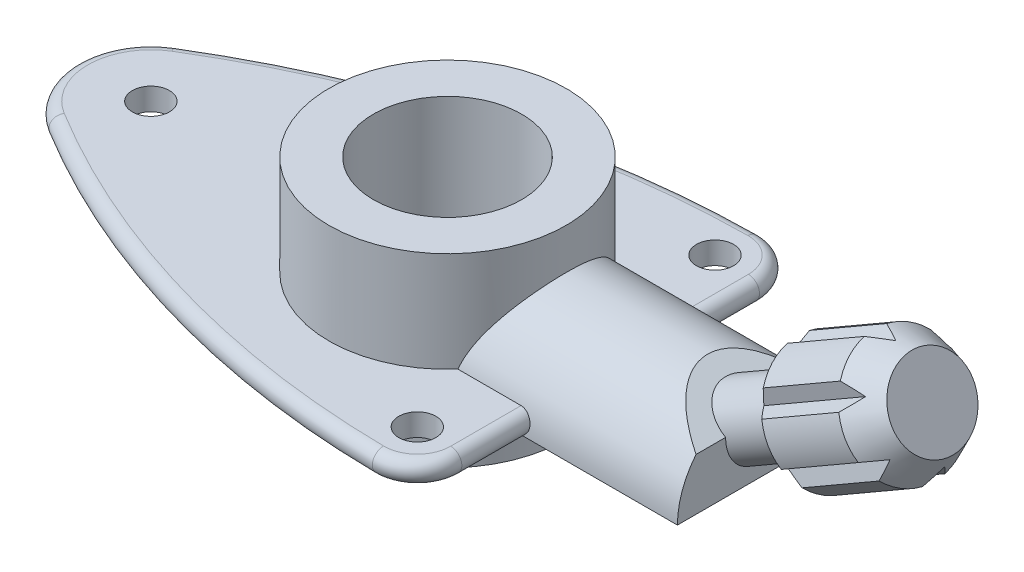
SolidWorks part; units mm, degrees
ref_plane "前视基准面" through (0, 0, 0) normal (0, 0, 1) x (1, 0, 0)
ref_plane "上视基准面" through (0, 0, 0) normal (0, 1, 0) x (1, 0, 0)
ref_plane "右视基准面" through (0, 0, 0) normal (1, 0, 0) x (0, 0, -1)
other "Configuration Table"
sketch "草图5" plane through (0, 0, 0) normal (0, 1, 0) x (1, 0, 0)
  line L0 (22, 20.0702) -> (22, -12.9012)
  line L1 (-61.685, 0) -> (42.0695, 0) construction
  line L3 (22, -20.0702) -> (22, 12.9012)
  line L4 (15.9338, 26.0698) -> (-45.2053, 8.5384) construction
  line L5 (15.9338, -26.0698) -> (-45.2053, -8.5384) construction
  circle A0 centre (0, 0) radius 10
  circle A1 centre (0, 0) radius 16
  arc A2 (22, 20.0702) -> (15.9338, 26.0698) centre (16, 20.0702) ccw
  arc A3 (15.9338, 26.0698) -> (-45.2053, 8.5384) centre (17.2581, -93.9229) ccw
  arc A4 (22, -20.0702) -> (15.9338, -26.0698) centre (16, -20.0702) cw
  arc A5 (15.9338, -26.0698) -> (-45.2053, -8.5384) centre (17.2581, 93.9229) cw
  arc A6 (-45.2053, 8.5384) -> (-45.2053, -8.5384) centre (-40, 0) ccw
  circle A7 centre (16, 20.0702) radius 2.5
  circle A8 centre (16, -20.0702) radius 2.5
  circle A9 centre (-40, 0) radius 2.5
  point P12 (-50, 0)
  dimension "D2" = 6
  dimension "D3" = 120
  dimension "D6" = 32
  dimension "D7" = 20
  dimension "D8" = 10
  dimension "D9" = 5
  dimension "D1" = 22
  dimension "D4" = 16
  dimension "D5" = 72
extrude "凸台-拉伸4" add sketch "草图5" along normal mid plane 3 contours A3 A6 A5 A4 L3 L0 A2 A1 region at (21.111, 0, -16.4857)
extrude "凸台-拉伸5" add sketch "草图5<5>" against normal blind 10 and the other way blind 15 contours A1 A0 region at (-15.5475, 0, 0)
sketch "草图5<5>" plane through (0, 0, 0) normal (0, 1, 0) x (1, 0, 0) same geometry as "草图5"
sketch "草图7" plane through (0, 0, 0) normal (1, 0, 0) x (0, 0, -1)
  line L0 (0, 27.4984) -> (0, -26.9284) construction
  line L1 (-11, -1.5) -> (11, -1.5)
  line L2 (-20.0702, -1.5) -> (20.0702, -1.5) construction
  line L6 (-16, -1.5) -> (16, -1.5) construction
  arc A0 (-11, -1.5) -> (11, -1.5) centre (0, -1.5) cw
  dimension "D1" = 22
extrude "凸台-拉伸8" add sketch "草图7" against normal up to surface (30.381 mm away) from offset 42 contours L0 A0 L1 | A0 L0 L1 region at (0, 3.1685, -4.6685) region at (0, 3.1685, 4.6685) up to face at (0, 1.5, 16)
fillet "圆角3" 2 edges at (-15.8184, 1.5, 21.4285) (-15.8184, -1.5, 21.4285) type full round first side face at (-40, 1.5, 2.5) second side face at (0, -1.5, 16) middle face at (-15.2271, 0, 19.3663)
sketch "草图10" plane through (0, 0, 0) normal (0, 0, 1) x (1, 0, 0)
  line L0 (35.0718, 9.5) -> (42, 5.5)
  line L1 (42, 9.5) -> (16, 9.5) construction
  line L2 (42, -1.5) -> (42, 9.5) construction
  line L3 (20.5, -1.5) -> (42, -1.5) construction
  dimension "D1" = 7
  dimension "D2" = 60
extrude "切除-拉伸1" cut sketch "草图10" against normal through all both and the other way through all
ref_plane "基准面2" through (33.8816, 19.5615, 0) normal (0.866, 0.5, 0) x (0, 0, -1)
sketch "草图12" plane through (33.8816, 19.5615, 0) normal (0.866, 0.5, 0) x (0, 0, -1)
  line L0 (0, 0) -> (0, -27.3995) construction
  line L1 (-8.4853, -16.2369) -> (8.4853, -16.2369) construction
  circle A0 centre (0, -16.2369) radius 4.5
  point P5 (0, 0)
  dimension "D1" = 9
extrude "凸台-拉伸10" add sketch "草图12" along normal blind 27 and the other way offset from surface 1 other way up to face at (0, -1.5, 16)
sketch "草图14" plane through (0, 0, 0) normal (0, 0, 1) x (1, 0, 0)
  line L0 (45.9593, 12.9821) -> (47.2404, 17.7631)
  line L1 (63.1327, 22.8971) -> (37.5, 8.0981) construction
  line L2 (47.2404, 17.7631) -> (57.6327, 23.7631)
  line L3 (63.1327, 22.8971) -> (62.6327, 23.7631)
  line L4 (42, 5.5) -> (65.3827, 19) construction
  line L5 (62.6327, 23.7631) -> (57.6327, 23.7631)
  line L6 (67.6327, 15.1029) -> (63.1327, 22.8971) construction
  line L7 (63.1327, 22.8971) -> (45.9593, 12.9821)
  dimension "D1" = 12
  dimension "D2" = 1
  dimension "D3" = 45
  dimension "D4" = 30
  dimension "D5" = 8
revolve "旋转1" add sketch "草图14" angle 360 about axis through (14.2076, -10.5459, 0) along (0.866, 0.5, 0)
sketch "草图15" plane through (57.2643, 33.0615, 0) normal (0.866, 0.5, 0) x (0, 0, -1)
  line L0 (0, 0) -> (0, -28.4818) construction
  line L1 (-1.5, -8.3787) -> (0, -9.6374)
  line L2 (0, -9.6374) -> (1.5, -8.3787)
  line L3 (5.7153, -12.9371) -> (7.5553, -13.6068)
  line L4 (6.0553, -11.0088) -> (5.7153, -12.9371)
  line L5 (5.7153, -19.5366) -> (6.0553, -21.465)
  line L6 (7.5553, -18.8669) -> (5.7153, -19.5366)
  line L7 (0, -22.8363) -> (-1.5, -24.095)
  line L8 (1.5, -24.095) -> (0, -22.8363)
  line L9 (-5.7153, -19.5366) -> (-7.5553, -18.8669)
  line L10 (-6.0553, -21.465) -> (-5.7153, -19.5366)
  line L11 (-5.7153, -12.9371) -> (-6.0553, -11.0088)
  line L12 (-7.5553, -13.6068) -> (-5.7153, -12.9371)
  circle A0 centre (0, -16.2369) radius 8 construction
  arc A1 (1.5, -8.3787) -> (-1.5, -8.3787) centre (0, -16.2369) ccw
  arc A2 (7.5553, -13.6068) -> (6.0553, -11.0088) centre (0, -16.2369) ccw
  arc A3 (6.0553, -21.465) -> (7.5553, -18.8669) centre (0, -16.2369) ccw
  arc A4 (-1.5, -24.095) -> (1.5, -24.095) centre (0, -16.2369) ccw
  arc A5 (-7.5553, -18.8669) -> (-6.0553, -21.465) centre (0, -16.2369) ccw
  arc A6 (-6.0553, -11.0088) -> (-7.5553, -13.6068) centre (0, -16.2369) ccw
  point P26 (0, -16.2369)
  dimension "D1" = 100
  dimension "D2" = 3
  dimension "D3" = 6
extrude "切除-拉伸2" cut sketch "草图15" against normal up to next
